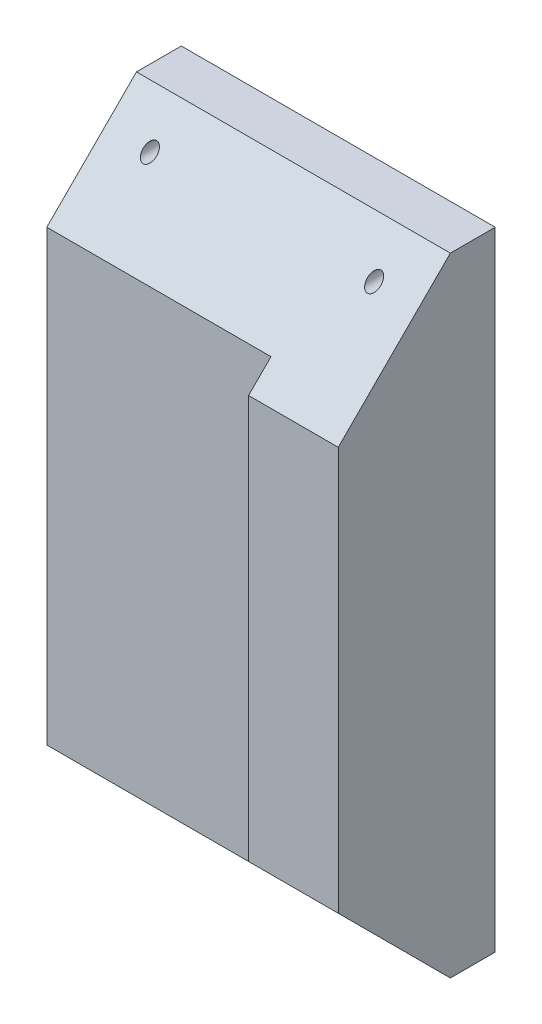
SolidWorks part; units mm, degrees
ref_plane "前视基准面" through (0, 0, 0) normal (0, 0, 1) x (1, 0, 0)
ref_plane "上视基准面" through (0, 0, 0) normal (0, 1, 0) x (1, 0, 0)
ref_plane "右视基准面" through (0, 0, 0) normal (1, 0, 0) x (0, 0, -1)
sketch "草图1" plane through (0, 0, 0) normal (0, 0, 1) x (1, 0, 0)
  line L1 (-65.0239, 99.0798) -> (4.9761, 99.0798)
  line L2 (-65.0239, 99.0798) -> (-65.0239, -40.9202)
  line L3 (-65.0239, -40.9202) -> (4.9761, -40.9202)
  line L4 (4.9761, 99.0798) -> (4.9761, -40.9202)
  dimension "D1" = 140
  dimension "D2" = 70
extrude "凸台-拉伸1" add sketch "草图1" along normal blind 10
sketch "草图2" plane through (0, 0, 10) normal (0, 0, 1) x (1, 0, 0)
  line L0 (4.9761, 99.0798) -> (-65.0239, 99.0798) construction
  line L1 (-65.0239, 79.0798) -> (-15.0239, 79.0798)
  line L2 (-65.0239, 79.0798) -> (-65.0239, -20.9202)
  line L3 (-65.0239, -20.9202) -> (-15.0239, -20.9202)
  line L4 (-15.0239, 79.0798) -> (-15.0239, -20.9202)
  line L5 (-65.0239, -40.9202) -> (4.9761, -40.9202) construction
  line L6 (-65.0239, 99.0798) -> (-65.0239, -40.9202) construction
  line L7 (4.9761, -40.9202) -> (4.9761, 99.0798) construction
  point P6 (-30.0239, -40.9202)
  dimension "D1" = 20
  dimension "D2" = 20
  dimension "D3" = 0
  dimension "D4" = 20
extrude "凸台-拉伸2" add sketch "草图2" along normal blind 20
chamfer "倒角2" distance 20 angle 45 1 edges
chamfer "倒角3" distance 20 angle 45 1 edges
sketch "草图3" plane through (0, 0, 10) normal (0, 0, 1) x (1, 0, 0)
  line L0 (4.9761, 99.0798) -> (-15.0239, 99.0798) construction
  line L1 (-15.0239, 99.0798) -> (4.9761, 99.0798)
  line L2 (-15.0239, 99.0798) -> (-15.0239, -40.9202)
  line L3 (-15.0239, -40.9202) -> (4.9761, -40.9202)
  line L4 (4.9761, 99.0798) -> (4.9761, -40.9202)
  line L5 (-15.0239, -40.9202) -> (-15.0239, 99.0798) construction
  dimension "D1" = 0
  dimension "D2" = 0
extrude "凸台-拉伸3" add sketch "草图3" along normal blind 25
sketch "草图4" plane through (-15.0239, 0, 0) normal (-1, 0, 0) x (0, 0, 1)
  line L0 (10, -40.9202) -> (42.0658, -8.8544)
  line L1 (42.0658, -8.8544) -> (42.0658, -55.2806)
  line L2 (42.0658, -55.2806) -> (10, -40.9202)
  line L3 (10, 99.0798) -> (42.0658, 67.014)
  line L4 (10, 99.0798) -> (30, 79.0798) construction
  line L5 (30, 79.0798) -> (10, 99.0798) construction
  line L6 (42.0658, 67.014) -> (50.9633, 103.9231)
  line L7 (50.9633, 103.9231) -> (10, 99.0798)
extrude "切除-拉伸1" cut sketch "草图4" against normal blind 25
sketch "草图5" plane through (0, 0, 0) normal (0, 0, -1) x (-1, 0, 0)
  circle A0 centre (5.0239, 92.0798) radius 1.5
  circle A1 centre (55.0239, 92.0798) radius 1.5
  circle A2 centre (5.0239, -33.9202) radius 1.5
  circle A3 centre (55.0239, -33.9202) radius 1.5
  dimension "D3" = 3
  dimension "D4" = 3
  dimension "D5" = 3
  dimension "D6" = 3
  dimension "D1" = 50
  dimension "D2" = 126
extrude "切除-拉伸2" cut sketch "草图5" against normal blind 25
